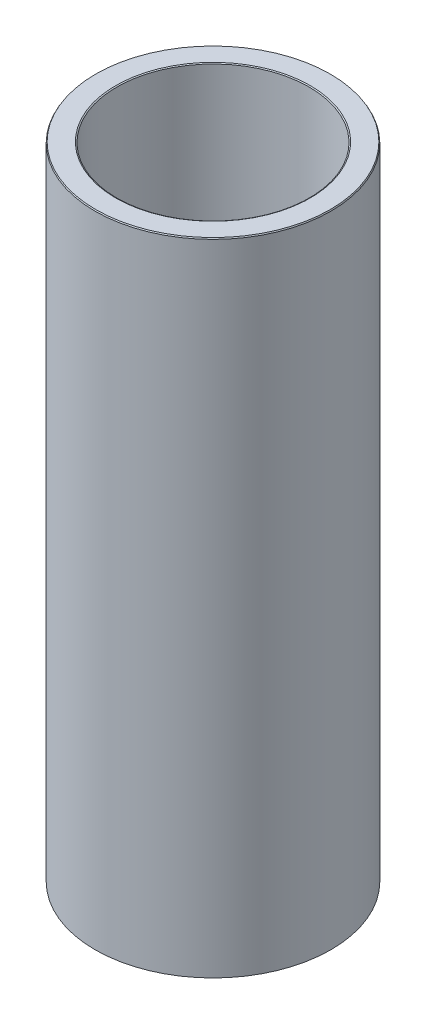
SolidWorks part; units mm, degrees
ref_plane "Front Plane" through (0, 0, 0) normal (0, 0, 1) x (1, 0, 0)
ref_plane "Top Plane" through (0, 0, 0) normal (0, 1, 0) x (1, 0, 0)
ref_plane "Right Plane" through (0, 0, 0) normal (1, 0, 0) x (0, 0, -1)
sketch "Sketch1" plane through (0, 0, 0) normal (0, 1, 0) x (1, 0, 0)
  circle A0 centre (0, 0) radius 30
  dimension "SLEEVE_OD" = 60
extrude "Boss-Extrude1" add sketch "Sketch1" along normal blind 163.1227
sketch "Sketch2" plane through (0, 0, 0) normal (0, 1, 0) x (1, 0, 0)
  circle A0 centre (0, 0) radius 24.4668
  dimension "BORE_D" = 48.9336
extrude "Cut-Extrude1" cut sketch "Sketch2" along normal through all
chamfer "Chamfer1" distance 0.2874 angle 30 4 edges at (0, 163.1227, 24.4668) (0, 0, 24.4668) (0, 0, 30) (0, 163.1227, 30) first distance on face at (0, 163.1227, 24.4668) first distance on face at (0, 0, 24.4668) first distance on face at (0, 163.1227, 30)
